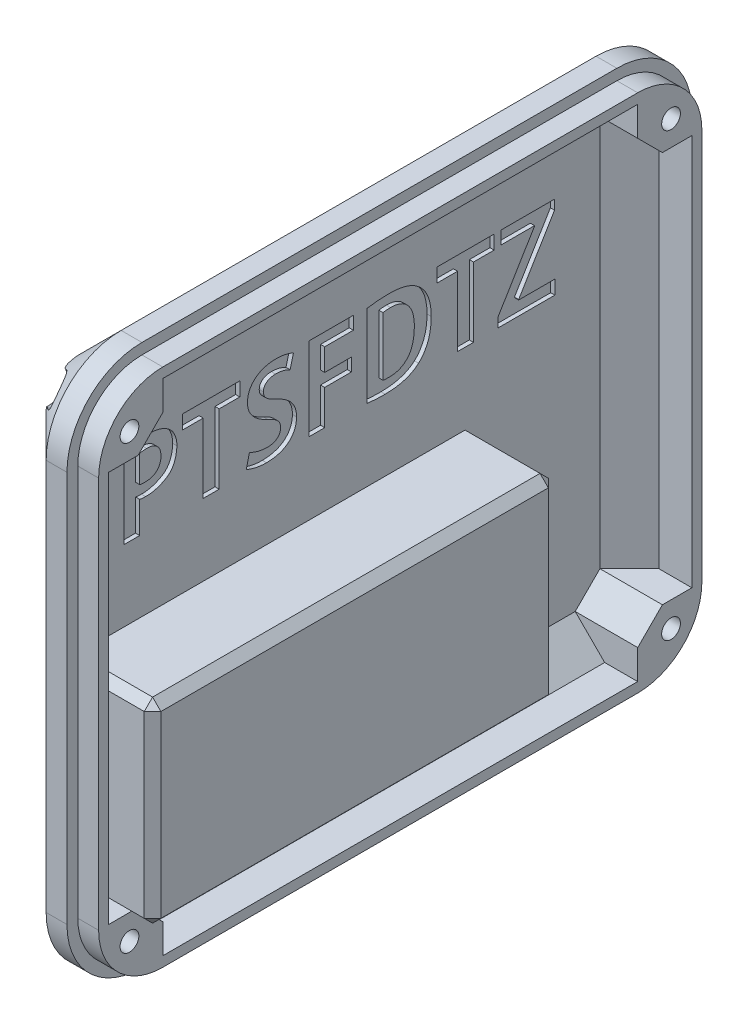
SolidWorks part; units mm, degrees
ref_plane "前视基准面" through (0, 0, 0) normal (0, 0, 1) x (1, 0, 0)
ref_plane "上视基准面" through (0, 0, 0) normal (0, 1, 0) x (1, 0, 0)
ref_plane "右视基准面" through (0, 0, 0) normal (1, 0, 0) x (0, 0, -1)
other "Configuration Table"
sketch "草图3" plane through (0, 0, 0) normal (1, 0, 0) x (0, 0, -1)
  line L1 (-57, -65) -> (57, -65)
  line L2 (-75, -47) -> (-75, 47)
  line L3 (-57, 65) -> (57, 65)
  line L4 (75, -47) -> (75, 47)
  line L5 (-75, -65) -> (75, 65) construction
  line L6 (-75, 65) -> (75, -65) construction
  arc A0 (57, -65) -> (75, -47) centre (57, -47) ccw
  arc A1 (-75, 47) -> (-57, 65) centre (-57, 47) cw
  arc A2 (-57, -65) -> (-75, -47) centre (-57, -47) cw
  arc A3 (57, 65) -> (75, 47) centre (57, 47) cw
  point P0 (0, 0)
  dimension "D3" = 18
  dimension "D1" = 150
  dimension "D2" = 130
extrude "凸台-拉伸4" add sketch "草图3" along normal blind 15
chamfer "倒角2" distance 10 angle 45 8 edges at (0, 0, -75) (0, 59.7279, -69.7279) (0, 65, 0) (0, 59.7279, 69.7279) (0, 0, 75) (0, -59.7279, 69.7279) (0, -65, 0) (0, -59.7279, -69.7279)
shell "抽壳3" thickness 5 removed face at (15, 0, 0)
sketch "草图4" plane through (15, 0, 0) normal (1, 0, 0) x (0, 0, -1)
  line L17 (70, -47) -> (70, 47)
  line L18 (57, 60) -> (-57, 60)
  line L19 (-70, 47) -> (-70, -47)
  line L20 (72.4, -47) -> (72.4, 47)
  line L21 (-57, -62.4) -> (57, -62.4)
  line L22 (-72.4, 47) -> (-72.4, -47)
  line L23 (57, 62.4) -> (-57, 62.4)
  line L24 (72.4, -47) -> (72.4, 47)
  line L25 (-57, -62.4) -> (57, -62.4)
  line L26 (-72.4, 47) -> (-72.4, -47)
  line L27 (57, 62.4) -> (-57, 62.4)
  line L28 (-57, -60) -> (57, -60)
  arc A22 (70, 47) -> (57, 60) centre (57, 47) ccw
  arc A23 (-57, 60) -> (-70, 47) centre (-57, 47) ccw
  arc A24 (57, -62.4) -> (72.4, -47) centre (57, -47) ccw
  arc A25 (-72.4, -47) -> (-57, -62.4) centre (-57, -47) ccw
  arc A26 (-57, 62.4) -> (-72.4, 47) centre (-57, 47) ccw
  arc A27 (72.4, 47) -> (57, 62.4) centre (57, 47) ccw
  arc A28 (57, -62.4) -> (72.4, -47) centre (57, -47) ccw
  arc A29 (-72.4, -47) -> (-57, -62.4) centre (-57, -47) ccw
  arc A30 (-57, 62.4) -> (-72.4, 47) centre (-57, 47) ccw
  arc A31 (72.4, 47) -> (57, 62.4) centre (57, 47) ccw
  arc A32 (-70, -47) -> (-57, -60) centre (-57, -47) ccw
  arc A33 (57, -60) -> (70, -47) centre (57, -47) ccw
  dimension "D1" = 2.4
  dimension "D2" = 2.4
extrude "凸台-拉伸5" add sketch "草图4" along normal blind 5
sketch "草图5" plane through (20, 0, 0) normal (1, 0, 0) x (0, 0, -1)
  line L0 (-57, 52.9289) -> (-62.9289, 47)
  line L1 (-62.9289, -47) -> (-62.9289, 47) construction
  line L2 (-62.9289, 47) -> (-70, 47)
  line L3 (-57, 60) -> (-57, 52.9289)
  line L4 (0, 0) -> (0, 60) construction
  line L5 (57, 60) -> (-57, 60) construction
  line L6 (0, 0) -> (-70, 0) construction
  line L7 (-70, 47) -> (-70, -47) construction
  line L8 (57, 60) -> (57, 52.9289)
  line L9 (57, 52.9289) -> (62.9289, 47)
  line L10 (62.9289, 47) -> (70, 47)
  line L11 (62.9289, -47) -> (70, -47)
  line L12 (57, -52.9289) -> (62.9289, -47)
  line L13 (57, -60) -> (57, -52.9289)
  line L14 (-57, -60) -> (-57, -52.9289)
  line L15 (-57, -52.9289) -> (-62.9289, -47)
  line L16 (-62.9289, -47) -> (-70, -47)
  arc A0 (-57, 52.9289) -> (-62.9289, 47) centre (-57, 47) ccw construction
  arc A1 (-57, 60) -> (-70, 47) centre (-57, 47) ccw
  arc A2 (57, 60) -> (70, 47) centre (57, 47) cw
  arc A3 (57, -60) -> (70, -47) centre (57, -47) ccw
  arc A4 (-57, -60) -> (-70, -47) centre (-57, -47) cw
extrude "凸台-拉伸6" add sketch "草图5" against normal up to next
sketch "草图6" plane through (20, 0, 0) normal (1, 0, 0) x (0, 0, -1)
  line L0 (57, 65) -> (-57, 65) construction
  line L1 (75, -47) -> (75, 47) construction
  line L2 (0, 0) -> (0, 60) construction
  line L3 (57, 60) -> (-57, 60) construction
  line L4 (0, 0) -> (-70, 0) construction
  line L5 (-70, 47) -> (-70, -47) construction
  circle A0 centre (65, 53) radius 2.25
  circle A1 centre (-65, 53) radius 2.25
  circle A2 centre (65, -53) radius 2.25
  circle A3 centre (-65, -53) radius 2.25
  dimension "D1" = 4.5
  dimension "D2" = 12
  dimension "D3" = 10
extrude "切除-拉伸1" cut sketch "草图6" against normal blind 43
sketch "草图7" plane through (0, 0, 0) normal (-1, 0, 0) x (0, 0, 1)
  line L0 (0, 0) -> (0, 55) construction
  line L1 (57, 55) -> (-57, 55) construction
  line L2 (0, 0) -> (-65, 0) construction
  line L3 (-65, 47) -> (-65, -47) construction
  circle A0 centre (65, 53) radius 3.75
  circle A1 centre (-65, 53) radius 3.75
  circle A2 centre (-65, -53) radius 3.75
  circle A3 centre (65, -53) radius 3.75
  dimension "D1" = 7.5
extrude "切除-拉伸2" cut sketch "草图7" against normal blind 16
fillet "圆角1" radius 2 4 edges at (0, -50.75, 62) (0, -50.75, -62) (0, 50.75, -62) (0, 50.75, 62)
sketch "草图8" plane through (0, 0, 0) normal (-1, 0, 0) x (0, 0, 1)
  line L0 (-57, -55) -> (57, -55) construction
  line L1 (-30.5511, -47) -> (62.4489, -47)
  line L2 (-30.5511, -47) -> (-30.5511, -4)
  line L3 (-30.5511, -4) -> (62.4489, -4)
  line L4 (62.4489, -47) -> (62.4489, -4)
  line L5 (-30.5511, -47) -> (62.4489, -4) construction
  line L6 (-30.5511, -4) -> (62.4489, -47) construction
  point P0 (15.9489, -25.5)
  point P8 (0, -25.5)
  point P9 (0, 0)
  dimension "D1" = 43
  dimension "D2" = 93
  dimension "D3" = 8
extrude "切除-拉伸3" cut sketch "草图8" against normal blind 16
sketch "草图12" plane through (5, 0, 0) normal (1, 0, 0) x (0, 0, -1)
  line L0 (-64.4489, -2) -> (-64.4489, -49)
  line L1 (-62.4489, -4) -> (30.5511, -4)
  line L2 (-62.4489, -4) -> (-62.4489, -47)
  line L3 (-62.4489, -47) -> (30.5511, -47)
  line L4 (30.5511, -4) -> (30.5511, -47)
  line L5 (-64.4489, -49) -> (32.5511, -49)
  line L6 (32.5511, -2) -> (32.5511, -49)
  line L7 (-64.4489, -2) -> (32.5511, -2)
  dimension "D1" = 2
extrude "凸台-拉伸7" add sketch "草图12" along normal blind 18
sketch "草图14" plane through (23, 0, 0) normal (1, 0, 0) x (0, 0, -1)
  line L1 (-64.4489, -2) -> (32.5511, -2)
  line L2 (-64.4489, -2) -> (-64.4489, -49)
  line L3 (-64.4489, -49) -> (32.5511, -49)
  line L4 (32.5511, -2) -> (32.5511, -49)
extrude "凸台-拉伸8" add sketch "草图14" along normal blind 2
chamfer "倒角4" distance 2 angle 45 8 edges at (25, -2, 15.9489) (15, -2, -32.5511) (25, -25.5, -32.5511) (15, -49, -32.5511) (25, -49, 15.9489) (22.5, -49, 64.4489) (25, -25.5, 64.4489) (15.76, -2, 64.4489)
sketch "草图15" plane through (0, 0, 0) normal (-1, 0, 0) x (0, 0, 1)
  line L0 (-57, -55) -> (57, -55) construction
  line L1 (-30.5511, -4) -> (-22.5511, -4)
  line L2 (-30.5511, -4) -> (-30.5511, 4)
  line L3 (-30.5511, 4) -> (-22.5511, 4)
  line L4 (-22.5511, -4) -> (-22.5511, 4)
  line L5 (-30.5511, -47) -> (-22.5511, -47)
  line L6 (-30.5511, -47) -> (-30.5511, -55)
  line L7 (-30.5511, -55) -> (-22.5511, -55)
  line L8 (-22.5511, -47) -> (-22.5511, -55)
  line L10 (62.4489, -4) -> (54.4489, -4)
  line L11 (62.4489, -4) -> (62.4489, 4)
  line L12 (62.4489, 4) -> (54.4489, 4)
  line L13 (54.4489, -4) -> (54.4489, 4)
  dimension "D1" = 8
  dimension "D2" = 8
  dimension "D3" = 8
  dimension "D4" = 8
  dimension "D5" = 8
extrude "切除-拉伸4" cut sketch "草图15" against normal blind 3
fillet "圆角2" radius 4 6 edges at (1.5, 4, 62.4489) (1.5, 4, 54.4489) (1.5, -55, -22.5511) (1.5, -55, -30.5511) (1.5, 4, -22.5511) (1.5, 4, -30.5511)
sketch "草图17" plane through (5, 0, 0) normal (1, 0, 0) x (0, 0, -1)
  text T0 "<b>PTSFDTZ</b>" font "@Adobe Gothic Std B" height 20
extrude "切除-拉伸5" cut sketch "草图17" against normal blind 1
